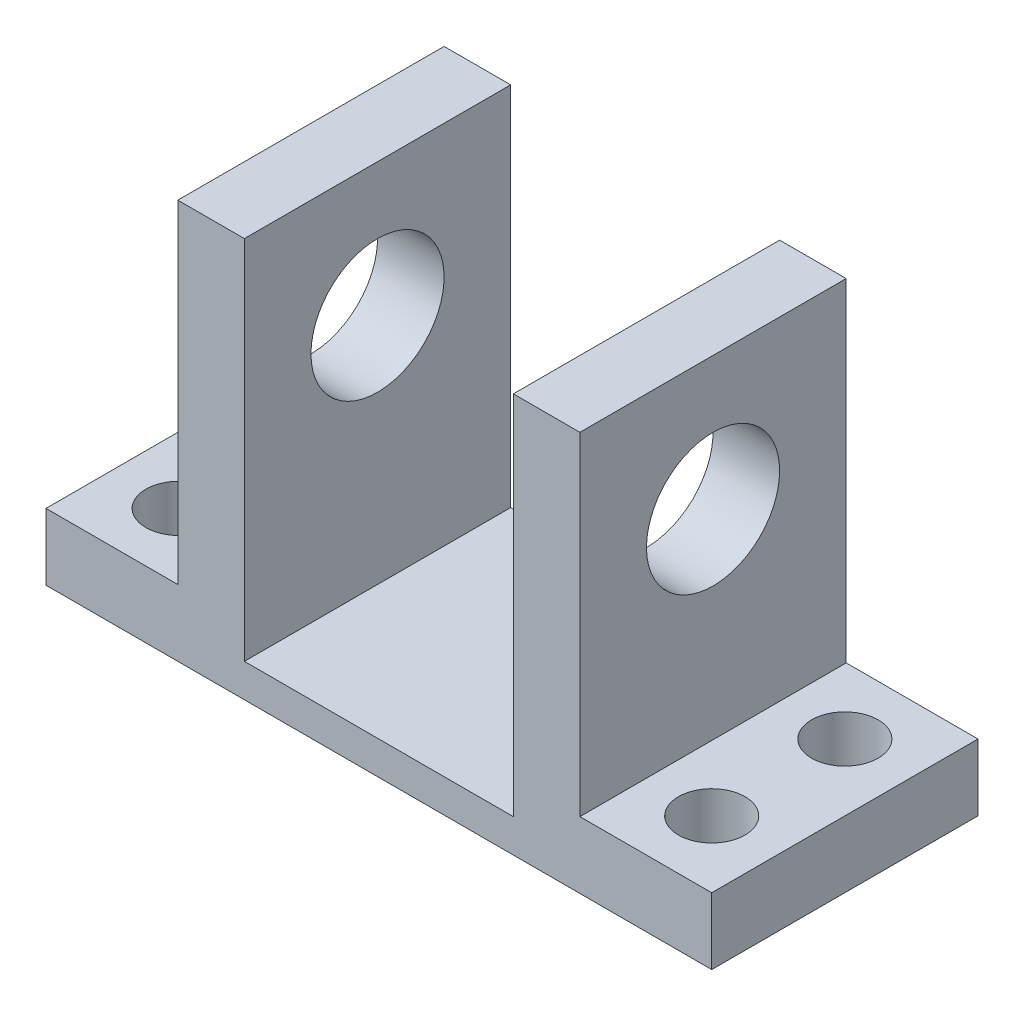
SolidWorks part; units mm, degrees
ref_plane "Front Plane" through (0, 0, 0) normal (0, 0, 1) x (1, 0, 0)
ref_plane "Top Plane" through (0, 0, 0) normal (0, 1, 0) x (1, 0, 0)
ref_plane "Right Plane" through (0, 0, 0) normal (1, 0, 0) x (0, 0, -1)
sketch "Sketch2" plane through (0, 0, 0) normal (0, 1, 0) x (1, 0, 0)
  line L0 (6.35, 0) -> (6.35, 25.4)
  line L1 (0, 0) -> (38.1, 0)
  line L2 (0, 0) -> (0, 25.4)
  line L3 (0, 25.4) -> (38.1, 25.4)
  line L4 (38.1, 0) -> (38.1, 25.4)
  line L5 (31.75, 0) -> (31.75, 25.4)
  dimension "D1" = 38.1
  dimension "D2" = 25.4
  dimension "D3" = 6.35
  dimension "D4" = 6.35
extrude "Boss-Extrude1" add sketch "Sketch2" along normal blind 38.1 contours L3 L2 L1 L0 | L5 L1 L4 L3 region at (3.175, 0, -12.7) region at (34.925, 0, -12.7)
extrude "Boss-Extrude2" add sketch "Sketch2<3>" along normal blind 3.175 contours L1 L5 L3 L0 region at (19.05, 0, -12.7)
sketch "Sketch2<3>" plane through (0, 0, 0) normal (0, 1, 0) x (1, 0, 0) same geometry as "Sketch2"
sketch "Sketch3" plane through (0, 0, 0) normal (-1, 0, 0) x (0, 0, 1)
  line L0 (-12.7, 38.1) -> (-12.7, 25.4) construction
  line L1 (0, 38.1) -> (-25.4, 38.1) construction
  circle A0 centre (-12.7, 25.4) radius 6.35
  dimension "D2" = 12.7
  dimension "D1" = 12.7
extrude "Cut-Extrude1" cut sketch "Sketch3" against normal through all
sketch "Sketch4" plane through (0, 0, 0) normal (-1, 0, 0) x (0, 0, 1)
  line L0 (0, 38.1) -> (0, 0) construction
  line L1 (-25.4, 0) -> (0, 0)
  line L2 (-25.4, 0) -> (-25.4, 6.35)
  line L3 (-25.4, 6.35) -> (0, 6.35)
  line L4 (0, 0) -> (0, 6.35)
  dimension "D1" = 6.35
extrude "Boss-Extrude3" add sketch "Sketch4" along normal blind 12.7
sketch "Sketch9" plane through (38.1, 0, 0) normal (1, 0, 0) x (0, 0, -1)
  line L0 (25.4, 38.1) -> (25.4, 0) construction
  line L1 (0, 0) -> (25.4, 0)
  line L2 (0, 0) -> (0, 6.35)
  line L3 (0, 6.35) -> (25.4, 6.35)
  line L4 (25.4, 0) -> (25.4, 6.35)
  dimension "D1" = 6.35
extrude "Boss-Extrude5" add sketch "Sketch9" along normal blind 12.7
sketch "Sketch10" plane through (0, 6.35, 0) normal (0, 1, 0) x (1, 0, 0)
  line L0 (-12.7, 19.05) -> (50.8, 19.05) construction
  line L1 (-12.7, 0) -> (-12.7, 25.4) construction
  line L2 (50.8, 25.4) -> (50.8, 0) construction
  line L3 (-12.7, 6.35) -> (50.8, 6.35) construction
  line L4 (-12.7, 0) -> (0, 0) construction
  line L5 (-12.7, 25.4) -> (0, 25.4) construction
  dimension "D1" = 6.35
  dimension "D2" = 6.35
hole_wizard "1/4 (0.25) Diameter Hole1" positions "3DSketch3" profile "Sketch11" hole size "1/4" standard "ANSI Inch"
sketch3d "3DSketch3"
  line L0 (-12.7, 6.35, -19.05) -> (50.8, 6.35, -19.05) construction
  line L1 (-12.7, 6.35, -6.35) -> (50.8, 6.35, -6.35) construction
  point P0 (-6.35, 6.35, -19.05)
  point P4 (-6.35, 6.35, -6.35)
  point P8 (44.45, 6.35, -6.35)
  point P10 (44.45, 6.35, -19.05)
  dimension "D1" = 6.35
  dimension "D2" = 6.35
  dimension "D3" = 6.35
  dimension "D4" = 6.35
sketch "Sketch11" plane through (-6.35, 6.35, -19.05) normal (1, 0, 0) x (0, 0, 1)
  line L0 (0, 0) -> (0, 27.3077)
  line L1 (0, 27.3077) -> (3.175, 25.4)
  line L2 (3.175, 25.4) -> (3.175, 0)
  line L5 (3.175, 0) -> (0, 0)
  line L10 (0, 27.3077) -> (-3.175, 25.4) construction
  line L11 (0, -6.35) -> (0, 107.95) construction
  dimension "Hole Dia." = 6.35
  dimension "Hole Depth" = 25.4
  dimension "Drill Angle" = 118
sketch "Sketch13" plane through (6.35, 0, 0) normal (1, 0, 0) x (0, 0, -1)
  line L1 (0, 3.175) -> (25.4, 3.175)
  line L2 (0, 3.175) -> (0, 38.1)
  line L3 (0, 38.1) -> (25.4, 38.1)
  line L4 (25.4, 3.175) -> (25.4, 38.1)
  circle A0 centre (12.7, 25.4) radius 6.35
  circle A1 centre (12.7, 25.4) radius 6.35 construction
  point P9 (0, 0)
extrude "Cut-Extrude2" cut sketch "Sketch13" against normal blind 0.127
sketch "Sketch14" plane through (31.75, 0, 0) normal (-1, 0, 0) x (0, 0, 1)
  line L1 (-25.4, 3.175) -> (0, 3.175)
  line L2 (-25.4, 3.175) -> (-25.4, 38.1)
  line L3 (-25.4, 38.1) -> (0, 38.1)
  line L4 (0, 3.175) -> (0, 38.1)
  circle A0 centre (-12.7, 25.4) radius 6.35
  circle A1 centre (-12.7, 25.4) radius 6.35 construction
extrude "Cut-Extrude3" cut sketch "Sketch14" against normal blind 0.127
sketch "Sketch15" plane through (0, 0, 0) normal (-1, 0, 0) x (0, 0, 1)
  line L1 (-25.4, 6.35) -> (0, 6.35)
  line L2 (-25.4, 6.35) -> (-25.4, 38.1)
  line L3 (-25.4, 38.1) -> (0, 38.1)
  line L4 (0, 6.35) -> (0, 38.1)
  circle A0 centre (-12.7, 25.4) radius 6.35
  circle A1 centre (-12.7, 25.4) radius 6.35 construction
sketch "Sketch16" plane through (38.1, 0, 0) normal (1, 0, 0) x (0, 0, -1)
  line L1 (0, 6.35) -> (25.4, 6.35)
  line L2 (0, 6.35) -> (0, 38.1)
  line L3 (0, 38.1) -> (25.4, 38.1)
  line L4 (25.4, 6.35) -> (25.4, 38.1)
  circle A0 centre (12.7, 25.4) radius 6.35
  circle A2 centre (12.7, 25.4) radius 6.35 construction
extrude "Boss-Extrude8" add sketch "Sketch16" along normal blind 0.127
extrude "Boss-Extrude9" add sketch "Sketch15" along normal blind 0.127
